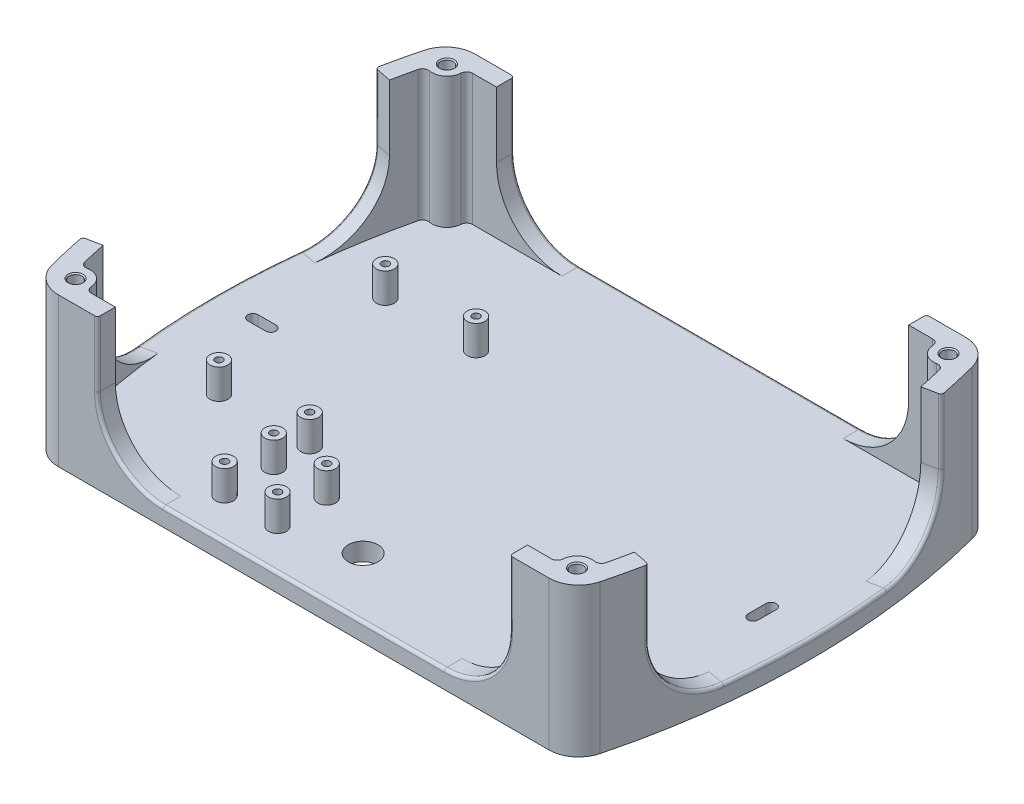
SolidWorks part; units mm, degrees
ref_plane "Front Plane" through (0, 0, 0) normal (0, 0, 1) x (1, 0, 0)
ref_plane "Top Plane" through (0, 0, 0) normal (0, 1, 0) x (1, 0, 0)
ref_plane "Right Plane" through (0, 0, 0) normal (1, 0, 0) x (0, 0, -1)
sketch "Sketch1" plane through (0, 0, 0) normal (0, 1, 0) x (1, 0, 0)
  line L0 (-100, 80) -> (-100, -80) construction
  line L1 (-90, 70) -> (90, 70)
  line L2 (-90, 70) -> (-90, -70) construction
  line L3 (-90, -70) -> (90, -70)
  line L4 (90, 70) -> (90, -70) construction
  line L5 (-90, 70) -> (90, -70) construction
  line L6 (-90, -70) -> (90, 70) construction
  line L8 (100, 80) -> (100, -80) construction
  line L10 (-100, -80) -> (100, -80) construction
  line L11 (-100, 80) -> (100, 80) construction
  arc A0 (-90, 70) -> (-90, -70) centre (150, 0) ccw
  arc A1 (90, 70) -> (90, -70) centre (-150, 0) cw
  point P0 (0, 0)
  dimension "D1" = 180
  dimension "D2" = 140
  dimension "D3" = 10
extrude "Boss-Extrude1" add sketch "Sketch1" along normal blind 50
fillet "Fillet5" radius 10 4 edges at (-90, 25, 70) (90, 25, 70) (90, 25, -70) (-90, 25, -70)
shell "Shell1" thickness 6 removed face at (0, 50, 0)
sketch "Sketch18" plane through (0, 50, 0) normal (0, 1, 0) x (1, 0, 0)
  line L0 (-88.5027, 67.9057) -> (-82.379, 60) construction
  line L1 (88.5027, 67.9057) -> (82.379, 60) construction
  line L2 (-88.5027, -67.9057) -> (-82.379, -60) construction
  line L3 (88.5027, -67.9057) -> (82.379, -60) construction
  arc A1 (82.379, -70) -> (92.0615, -62.5) centre (82.379, -60) ccw construction
  arc A3 (-82.379, 70) -> (-92.0615, 62.5) centre (-82.379, 60) ccw construction
  circle A4 centre (-84.2161, 62.3717) radius 5
  circle A5 centre (84.2161, 62.3717) radius 5
  circle A6 centre (84.2161, -62.3717) radius 5
  circle A7 centre (-84.2161, -62.3717) radius 5
  arc A8 (92.0615, 62.5) -> (82.379, 70) centre (82.379, 60) ccw construction
  arc A9 (-92.0615, -62.5) -> (-82.379, -70) centre (-82.379, -60) ccw construction
  point P24 (-84.2161, 62.3717)
  point P25 (84.2161, 62.3717)
  point P27 (-84.2161, -62.3717)
  dimension "D5" = 10
  dimension "D6" = 10
  dimension "D7" = 10
  dimension "D8" = 10
  dimension "D9" = 0
  dimension "D1" = 7
  dimension "D2" = 7
  dimension "D3" = 7
  dimension "D4" = 7
extrude "Boss-Extrude2" add sketch "Sketch18" against normal up to surface (44 mm away) contours A5 | A4 | A7 | A6 up to face at (0, 6, 0)
hole_wizard "CBORE for M5 Hex Head Bolt1" positions "Sketch19" profile "Sketch20" counterbore size "M5" standard "ANSI Metric"
sketch "Sketch19" plane through (0, 50, 0) normal (0, 1, 0) x (1, 0, 0)
  point P0 (-84.2161, 62.3717)
  point P3 (84.2161, 62.3717)
  point P6 (84.2161, -62.3717)
  point P9 (-84.2161, -62.3717)
sketch "Sketch20" plane through (-84.2161, 50, -62.3717) normal (1, 0, 0) x (0, 0, 1)
  line L0 (0, 0) -> (0, 10.9013)
  line L1 (0, 10.9013) -> (1.5, 10)
  line L2 (1.5, 10) -> (1.5, 4.375)
  line L3 (1.5, 4.375) -> (2.125, 4.375)
  line L5 (2.125, 4.375) -> (2.125, 0.375)
  line L6 (2.125, 0.375) -> (2.5, 0)
  line L7 (2.5, 0) -> (0, 0)
  line L8 (-2.125, 0.375) -> (-2.5, 0) construction
  line L10 (0, 10.9013) -> (-1.5, 10) construction
  line L11 (0, -6.35) -> (0, 107.95) construction
  dimension "Hole Dia." = 3
  dimension "Hole Depth" = 10
  dimension "C'Bore Dia." = 4.25
  dimension "C'Bore Depth" = 4.375
  dimension "Near C'Sink Dia." = 5
  dimension "Near C'Sink Angle" = 90
  dimension "Drill Angle" = 118
fillet "Fillet6" radius 2 8 edges at (-79.4887, 28, 64) (79.4887, 28, 64) (79.4887, 28, -64) (-79.4887, 28, -64) (86.9594, 28, 58.1915) (86.9594, 28, -58.1915) (-86.9594, 28, -58.1915) (-86.9594, 28, 58.1915)
sketch "Sketch21" plane through (0, 6, 0) normal (0, 1, 0) x (1, 0, 0)
  line L0 (0, 0) -> (-50000, 0) construction
  line L1 (0, -27.94) -> (-50000, -27.94) construction
  line L2 (0, -40) -> (-50000, -40) construction
  line L3 (-40, -1000) -> (-40, 49000) construction
  circle A0 centre (25, 0) radius 51 construction
  circle A1 centre (-40, -27.94) radius 3
  circle A2 centre (-40, -40) radius 3
  dimension "D1" = 102
  dimension "D6" = 6
  dimension "D7" = 6
  dimension "D2" = 25
  dimension "D5" = 40
  dimension "D3" = 27.94
  dimension "D4" = 40
extrude "Boss-Extrude3" add sketch "Sketch21" along normal blind 10 contours A1
hole_wizard "M3x0.5 Tapped Hole2" positions "Sketch22" profile "Sketch23" tap size "M3x0.5" standard "ANSI Metric"
sketch "Sketch22" plane through (0, 16, 0) normal (0, 1, 0) x (1, 0, 0)
  point P0 (-40, -27.94)
sketch "Sketch23" plane through (-40, 16, 27.94) normal (1, 0, 0) x (0, 0, 1)
  line L0 (0, 0) -> (0, 8.2511)
  line L1 (0, 8.2511) -> (1.25, 7.5)
  line L2 (1.25, 7.5) -> (1.25, 0)
  line L5 (1.25, 0) -> (0, 0)
  line L10 (0, 8.2511) -> (-1.25, 7.5) construction
  line L11 (0, -6.35) -> (0, 107.95) construction
  dimension "Tap Drill Dia." = 2.5
  dimension "Tap Drill Depth" = 7.5
  dimension "Drill Angle" = 118
pattern_linear "LPattern1" count 2 spacing 30.48 along (-1, 0, 0) count 2 spacing 55.88 along (0, 0, -1) of "Boss-Extrude3", "M3x0.5 Tapped Hole2"
extrude "Boss-Extrude4" add sketch "Sketch21<3>" along normal blind 10 separate body contours A2
sketch "Sketch21<3>" plane through (0, 6, 0) normal (0, 1, 0) x (1, 0, 0) same geometry as "Sketch21"
hole_wizard "M3x0.5 Tapped Hole3" positions "Sketch24" profile "Sketch25" tap size "M3x0.5" standard "ANSI Metric"
sketch "Sketch24" plane through (0, 16, 0) normal (0, 1, 0) x (1, 0, 0)
  point P0 (-40, -40)
sketch "Sketch25" plane through (-40, 16, 40) normal (1, 0, 0) x (0, 0, 1)
  line L0 (0, 0) -> (0, 8.2511)
  line L1 (0, 8.2511) -> (1.25, 7.5)
  line L2 (1.25, 7.5) -> (1.25, 0)
  line L5 (1.25, 0) -> (0, 0)
  line L10 (0, 8.2511) -> (-1.25, 7.5) construction
  line L11 (0, -6.35) -> (0, 107.95) construction
  dimension "Tap Drill Dia." = 2.5
  dimension "Tap Drill Depth" = 7.5
  dimension "Drill Angle" = 118
pattern_linear "LPattern3" count 2 spacing 16.51 along (0, 0, 1) count 2 spacing 17.78 along (1, 0, 0) of "Boss-Extrude4", "M3x0.5 Tapped Hole3"
ref_plane "Plane2" through (0, 50, 0) normal (0, 1, 0) x (1, 0, 0)
sketch "Sketch26" plane through (0, 6, 0) normal (0, 1, 0) x (1, 0, 0)
  line L0 (-87, 0) -> (-81, 0) construction
  line L1 (200000, 0) -> (-250000, 0) construction
  line L2 (-87, 1.7526) -> (-81, 1.7526)
  line L3 (-87, -1.7526) -> (-81, -1.7526)
  line L4 (84, 3) -> (84, -3) construction
  line L5 (85.7526, 3) -> (85.7526, -3)
  line L6 (82.2474, 3) -> (82.2474, -3)
  circle A0 centre (0, -50) radius 5
  arc A1 (-87, 1.7526) -> (-87, -1.7526) centre (-87, 0) ccw
  arc A2 (-81, -1.7526) -> (-81, 1.7526) centre (-81, 0) ccw
  arc A3 (85.7526, 3) -> (82.2474, 3) centre (84, 3) ccw
  arc A4 (82.2474, -3) -> (85.7526, -3) centre (84, -3) ccw
  point P7 (-84, 0)
  point P14 (84, 0)
  dimension "D1" = 10
  dimension "D5" = 84
  dimension "D7" = 1.7526
  dimension "D2" = 50
  dimension "D3" = 3.5052
  dimension "D4" = 6
  dimension "D6" = 6
  dimension "D8" = 84
extrude "Cut-Extrude5" cut sketch "Sketch26" against normal through all contours A0
extrude "Cut-Extrude7" cut sketch "Sketch26<4>" against normal through all contours A1 L3 A2 L2
sketch "Sketch26<4>" plane through (0, 6, 0) normal (0, 1, 0) x (1, 0, 0) same geometry as "Sketch26"
extrude "Cut-Extrude8" cut sketch "Sketch26<5>" against normal through all contours A4 L5 A3 L6
sketch "Sketch26<5>" plane through (0, 6, 0) normal (0, 1, 0) x (1, 0, 0) same geometry as "Sketch26"
sketch "Sketch27" plane through (0, 50, 0) normal (0, 1, 0) x (1, 0, 0)
  line L0 (-95.0991, 49.259) -> (-89.2167, 48.0768)
  line L1 (-95.0991, -49.259) -> (-89.2167, -48.0768)
  line L3 (69.2161, 70) -> (69.2161, 64)
  line L4 (95.0991, 49.259) -> (89.2167, 48.0768)
  line L6 (95.0991, -49.259) -> (89.2167, -48.0768)
  line L7 (69.2161, -64) -> (69.2161, -70)
  line L16 (-69.2161, 70) -> (-69.2161, 64)
  line L17 (82.379, 70) -> (-82.379, 70) construction
  line L18 (77.226, 64) -> (-77.226, 64) construction
  line L19 (-77.226, -64) -> (77.226, -64) construction
  line L20 (-82.379, -70) -> (82.379, -70) construction
  line L21 (-69.2161, -64) -> (-69.2161, -70)
  line L22 (-69.2161, -64) -> (69.2161, -64)
  line L23 (-69.2161, -70) -> (69.2161, -70)
  line L24 (-69.2161, 70) -> (69.2161, 70)
  line L25 (-69.2161, 64) -> (69.2161, 64)
  arc A0 (-92.0615, 62.5) -> (-92.0615, -62.5) centre (150, 0) ccw construction
  arc A1 (92.0615, -62.5) -> (92.0615, 62.5) centre (-150, 0) ccw construction
  arc A2 (-87.4966, 55.9586) -> (-87.4966, -55.9586) centre (150, 0) ccw construction
  arc A3 (-95.0991, -49.259) -> (-95.0991, 49.259) centre (150, 0) cw
  arc A4 (-89.2167, 48.0768) -> (-89.2167, -48.0768) centre (150, 0) ccw
  arc A5 (87.4966, -55.9586) -> (87.4966, 55.9586) centre (-150, 0) ccw construction
  arc A6 (89.2167, 48.0768) -> (89.2167, -48.0768) centre (-150, 0) cw
  arc A9 (-87.4966, 55.9586) -> (-87.4966, -55.9586) centre (150, 0) ccw construction
  arc A10 (95.0991, 49.259) -> (95.0991, -49.259) centre (-150, 0) cw
  dimension "D5" = 250
  dimension "D6" = 244
  dimension "D13" = 15
  dimension "D14" = 6
  dimension "D7" = 250
  dimension "D8" = 244
  dimension "D1" = 15
  dimension "D2" = 6
  dimension "D3" = 15
  dimension "D4" = 6
  dimension "D9" = 15
  dimension "D10" = 15
  dimension "D11" = 15
  dimension "D12" = 15
  dimension "D15" = 6
extrude "Cut-Extrude9" cut sketch "Sketch27" against normal blind 44
fillet "Fillet7" radius 22 8 edges at (-69.2161, 6, -67) (69.2161, 6, -67) (92.1579, 6, -48.6679) (92.1579, 6, 48.6679) (69.2161, 6, 67) (-69.2161, 6, 67) (-92.1579, 6, 48.6679) (-92.1579, 6, -48.6679)
fillet "Fillet8" radius 1 20 edges at (-69.2161, 39, 70) (-62.7725, 12.4437, 70) (69.2161, 39, 70) (62.7725, 12.4437, 70) (69.2161, 39, -70) (62.7725, 12.4437, -70) (-69.2161, 39, -70) (-62.7725, 12.4437, -70) (95.0991, 39, 49.259) (96.596, 10.8024, 41.1144) (95.0991, 39, -49.259) (96.0033, 14.2576, -44.5242) (-95.0991, 39, -49.259) (-96.596, 10.8024, -41.1144) (-95.0991, 39, 49.259) (-96.0033, 14.2576, 44.5242) (0, 6, 70) (0, 6, -70) (100, 6, 0) (-100, 6, 0)
